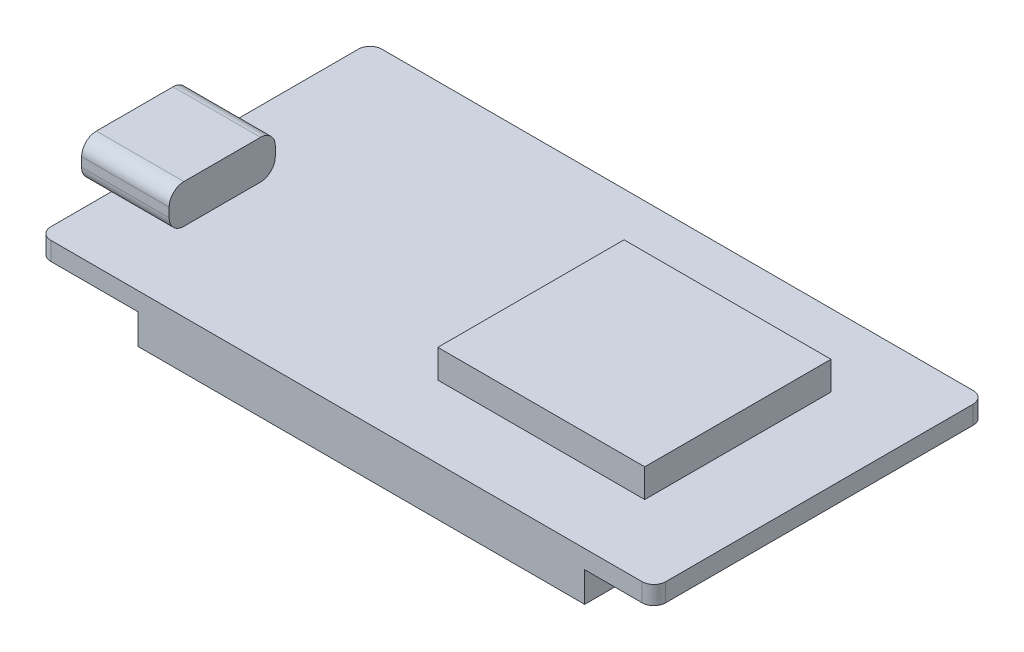
SolidWorks part; units mm, degrees
ref_plane "前基準面" through (0, 0, 0) normal (0, 0, 1) x (1, 0, 0)
ref_plane "上基準面" through (0, 0, 0) normal (0, 1, 0) x (1, 0, 0)
ref_plane "右基準面" through (0, 0, 0) normal (1, 0, 0) x (0, 0, -1)
sketch "草圖1" plane through (0, 0, 0) normal (0, 1, 0) x (1, 0, 0)
  line L1 (-26, 14) -> (26, 14)
  line L2 (-26, 14) -> (-26, -14)
  line L3 (-26, -14) -> (26, -14)
  line L4 (26, 14) -> (26, -14)
  line L5 (-26, 14) -> (26, -14) construction
  line L6 (-26, -14) -> (26, 14) construction
  point P0 (0, 0)
  dimension "D1" = 28
  dimension "D2" = 52
extrude "填料-伸長1" add sketch "草圖1" along normal blind 1.55
fillet "圓角1" radius 1 4 edges at (26, 0.775, -14) (-26, 0.775, -14) (-26, 0.775, 14) (26, 0.775, 14)
sketch "草圖2" plane through (0, 0, 0) normal (0, -1, 0) x (1, 0, 0)
  line L0 (-25, 14) -> (25, 14) construction
  line L1 (-17.61, 14) -> (20.15, 14)
  line L2 (-17.61, 14) -> (-17.61, 11.46)
  line L3 (-17.61, 11.46) -> (20.15, 11.46)
  line L4 (20.15, 14) -> (20.15, 11.46)
  line L5 (26, 13) -> (26, -13) construction
  line L6 (-26, 0) -> (26, 0) construction
  line L7 (-26, -13) -> (-26, 13) construction
  line L8 (20.15, -14) -> (20.15, -11.46)
  line L9 (-17.61, -14) -> (-17.61, -11.46)
  line L10 (-17.61, -14) -> (20.15, -14)
  line L11 (-17.61, -11.46) -> (20.15, -11.46)
  dimension "D1" = 2.54
  dimension "D2" = 37.76
  dimension "D3" = 5.85
extrude "填料-伸長2" add sketch "草圖2" along normal blind 2.54
sketch "草圖3" plane through (0, 1.55, 0) normal (0, 1, 0) x (1, 0, 0)
  line L0 (26, -13) -> (26, 13) construction
  line L1 (1.6, 7.875) -> (19.1, 7.875)
  line L2 (1.6, 7.875) -> (1.6, -7.875)
  line L3 (1.6, -7.875) -> (19.1, -7.875)
  line L4 (19.1, 7.875) -> (19.1, -7.875)
  line L5 (1.6, 7.875) -> (19.1, -7.875) construction
  line L6 (1.6, -7.875) -> (19.1, 7.875) construction
  point P0 (10.35, 0)
  dimension "D1" = 17.5
  dimension "D2" = 15.75
  dimension "D3" = 6.9
extrude "填料-伸長4" add sketch "草圖3" along normal blind 2.4
sketch "草圖5" plane through (-26, 0, 0) normal (-1, 0, 0) x (0, 0, 1)
  line L0 (-13, 1.55) -> (13, 1.55) construction
  line L1 (7.35, 1.55) -> (0.87, 1.55)
  line L2 (8.6, 2.8) -> (8.6, 3.58)
  line L3 (7.35, 4.83) -> (0.87, 4.83)
  line L4 (-0.38, 2.8) -> (-0.38, 3.58)
  line L5 (-7.875, 1.55) -> (7.875, 1.55) construction
  line L6 (14, 1.55) -> (14, 0) construction
  arc A0 (0.87, 4.83) -> (-0.38, 3.58) centre (0.87, 3.58) ccw
  arc A1 (0.87, 1.55) -> (-0.38, 2.8) centre (0.87, 2.8) cw
  arc A2 (7.35, 1.55) -> (8.6, 2.8) centre (7.35, 2.8) ccw
  arc A3 (8.6, 3.58) -> (7.35, 4.83) centre (7.35, 3.58) ccw
  point P13 (-0.38, 4.83)
  point P16 (-0.38, 1.55)
  point P19 (8.6, 1.55)
  point P22 (8.6, 4.83)
  dimension "D4" = 1.25
  dimension "D1" = 3.28
  dimension "D2" = 8.98
  dimension "D3" = 5.4
extrude "填料-伸長6" add sketch "草圖5" against normal blind 5.6 and the other way blind 1.8
